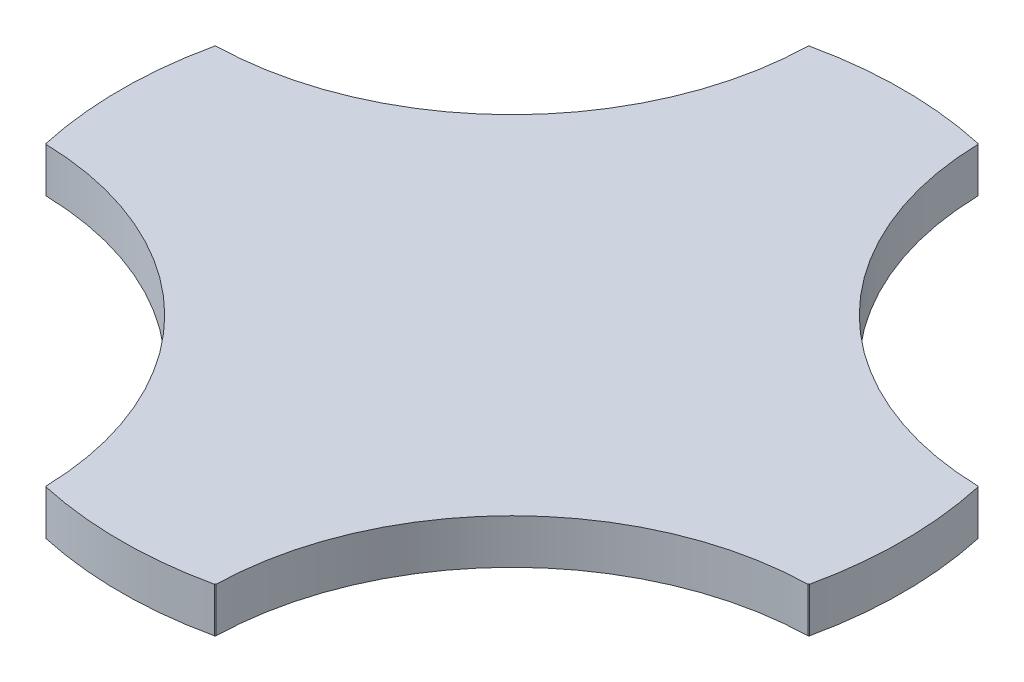
SolidWorks part; units mm, degrees
material "AISI 316 Annealed Stainless Steel Bar (SS)"
ref_plane "Front Plane" through (0, 0, 0) normal (0, 0, 1) x (1, 0, 0)
ref_plane "Top Plane" through (0, 0, 0) normal (0, 1, 0) x (1, 0, 0)
ref_plane "Right Plane" through (0, 0, 0) normal (1, 0, 0) x (0, 0, -1)
sketch "Sketch1" plane through (0, 0, 0) normal (0, 1, 0) x (1, 0, 0)
  line L0 (3.15, 0) -> (-3.15, 0) construction
  line L1 (0, 0) -> (3.1244, -3.1244) construction
  line L2 (3.0697, -0.685) -> (-3.0697, -0.685) construction
  line L3 (0.685, -3.0697) -> (0.685, 3.0697) construction
  line L4 (-0.685, -3.0697) -> (-0.685, 3.0697) construction
  line L5 (0, 0) -> (3.15, -0.685) construction
  line L6 (0, 0) -> (-0.685, -3.15) construction
  line L7 (-3.076, -0.6787) -> (-3.0697, -0.685)
  line L8 (-3.076, 0.6787) -> (-3.0697, 0.685)
  line L9 (0.6787, -3.076) -> (0.685, -3.0697)
  line L10 (0.6787, 3.076) -> (0.685, 3.0697)
  line L11 (-3.7547, 0) -> (3.7547, 0) construction
  line L12 (0, -3.7547) -> (0, 3.7547) construction
  line L13 (3.0697, -0.685) -> (3.076, -0.6787)
  line L14 (-0.685, -3.0697) -> (-0.6787, -3.076)
  line L15 (3.15, -0.685) -> (-3.15, -0.685) construction
  line L16 (0, 0) -> (3.1244, -3.1244) construction
  line L17 (-0.685, 3.0697) -> (-0.6787, 3.076)
  line L18 (3.0697, 0.685) -> (3.076, 0.6787)
  line L19 (3.0697, 0.685) -> (-3.0697, 0.685) construction
  arc A0 (3.076, -0.6787) -> (3.076, 0.6787) centre (0, 0) ccw
  arc A1 (-0.6787, -3.076) -> (0.6787, -3.076) centre (0, 0) ccw
  arc A2 (-3.076, 0.6787) -> (-3.076, -0.6787) centre (0, 0) ccw
  arc A3 (0.6787, 3.076) -> (-0.6787, 3.076) centre (0, 0) ccw
  arc A4 (3.1477, -0.6845) -> (0.685, -3.0697) centre (3.1244, -3.1244) ccw
  arc A5 (-0.685, -3.0697) -> (-3.0697, -0.685) centre (-3.1244, -3.1244) ccw
  arc A6 (-3.0697, 0.685) -> (-0.685, 3.0697) centre (-3.1244, 3.1244) ccw
  arc A7 (0.685, 3.0697) -> (3.0697, 0.685) centre (3.1244, 3.1244) ccw
  dimension "D1" = 6.3
  dimension "D2" = 4.88
  dimension "D5" = 90
  dimension "D6" = 3.2236
  dimension "D7" = 5.31
  dimension "D8" = 45
  dimension "D10" = 4.4186
  dimension "D3" = 0.685
  dimension "D4" = 2
  dimension "D9" = 4
extrude "Boss-Extrude1" add sketch "Sketch1" along normal blind 0.36 contours A7 L10 A3 L17 A6 L8 A2 L7 A5 L14 A1 L9 A4 L13 A0 L18 region at (0, 0, 0)
ref_axis "Axis1" through (0, 0.378, 0) along (0, -1, 0)
ref_plane "Plane1" through (0, 0, 0) normal (-0.7071, 0, 0.7071) x (0, -1, 0)
ref_plane "Plane2" through (0, 0, 0) normal (-0.7071, 0, -0.7071) x (0, -1, 0)
